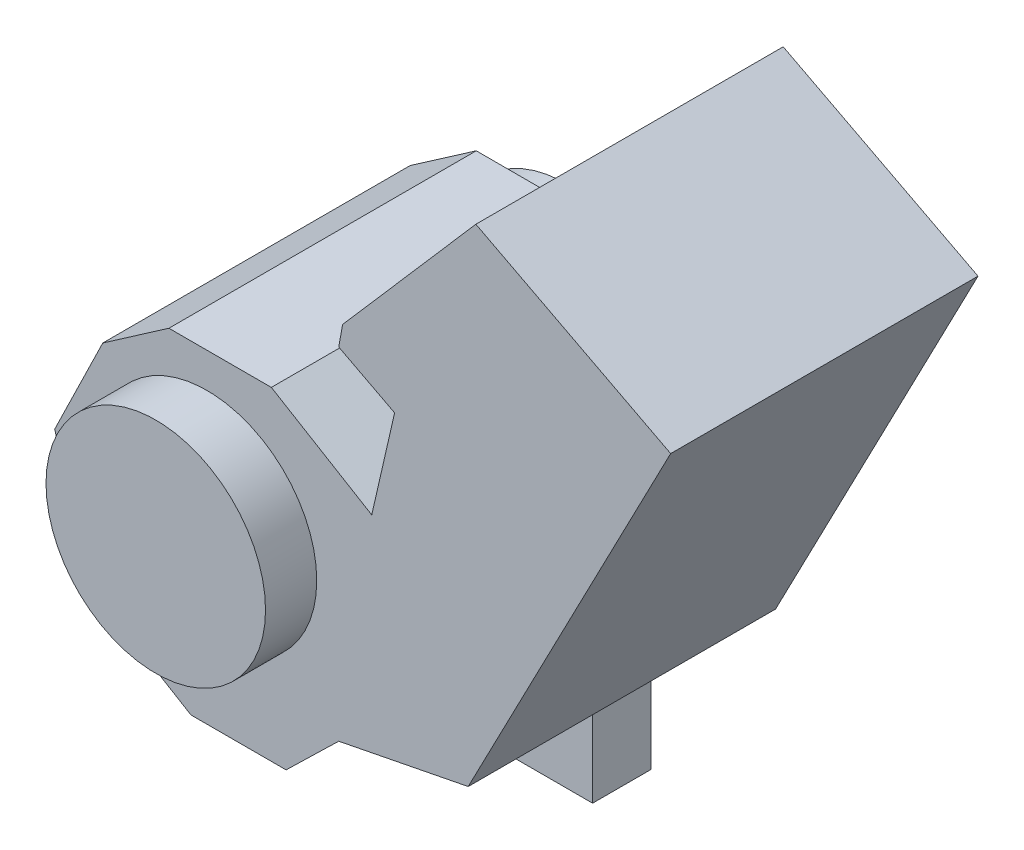
SolidWorks part; units mm, degrees
ref_plane "Plan de face" through (0, 0, 0) normal (0, 0, 1) x (1, 0, 0)
ref_plane "Plan de dessus" through (0, 0, 0) normal (0, 1, 0) x (1, 0, 0)
ref_plane "Plan de droite" through (0, 0, 0) normal (1, 0, 0) x (0, 0, -1)
sketch "Esquisse1" plane through (0, 0, 0) normal (0, 0, 1) x (1, 0, 0)
  line L0 (0, 0) -> (65, 0)
  line L1 (65, 0) -> (100.9635, 34.9393)
  line L2 (100.9635, 34.9393) -> (189.4354, 52.3577)
  line L3 (189.4354, 0) -> (65, 0)
  line L4 (189.4354, 52.3577) -> (327.7744, 318.5574)
  line L5 (327.7744, 318.5574) -> (194.6746, 387.7269)
  line L6 (194.6746, 387.7269) -> (103.6463, 282.9069)
  line L7 (103.6463, 282.9069) -> (100.9635, 268.2284)
  line L8 (100.9635, 268.2284) -> (139.1637, 248.3765)
  line L9 (139.1637, 248.3765) -> (123.5284, 180.145)
  line L10 (123.5284, 180.145) -> (54.9317, 221.3093)
  line L11 (54.9317, 221.3093) -> (-15.0683, 221.3093)
  line L12 (0, 0) -> (-68.5966, 41.1643)
  line L13 (-60.2666, 189.9707) -> (-93.1208, 122.5496)
  line L14 (-93.1208, 122.5496) -> (-68.5966, 41.1643)
  line L15 (-60.2666, 189.9707) -> (-15.0683, 221.3093)
  line L16 (189.4354, 0) -> (189.4354, 52.3577)
  circle A0 centre (10.9537, 122.5496) radius 75
  point P3 (10.9537, 122.5496)
  point P19 (258.6049, 185.4575)
  dimension "D13" = 150
  dimension "D1" = 65
  dimension "D2" = 135
  dimension "D3" = 80
  dimension "D4" = 75
  dimension "D5" = 85
  dimension "D6" = 55
  dimension "D7" = 70
  dimension "D8" = 80
  dimension "D9" = 70
  dimension "D10" = 150
  dimension "D11" = 150
  dimension "D12" = 300
extrude "Boss.-Extru.1" add sketch "Esquisse1" along normal blind 105 and the other way blind 105 contours L12 L4 L5 L6 L7 L8 L9 L10 L11 L15 region at (144.4714, 186.6884, 0)
extrude "Boss.-Extru.2" add sketch "Esquisse1<3>" along normal blind 20 and the other way blind 20 contours L3 L16 L2 L1 region at (139.8626, 20.6492, 0)
sketch "Esquisse1<3>" plane through (0, 0, 0) normal (0, 0, 1) x (1, 0, 0) same geometry as "Esquisse1"
extrude "Boss.-Extru.3" add sketch "Esquisse1<4>" along normal blind 140 and the other way blind 140 contours A0 region at (10.9537, 122.5496, 0)
sketch "Esquisse1<4>" plane through (0, 0, 0) normal (0, 0, 1) x (1, 0, 0) same geometry as "Esquisse1"
